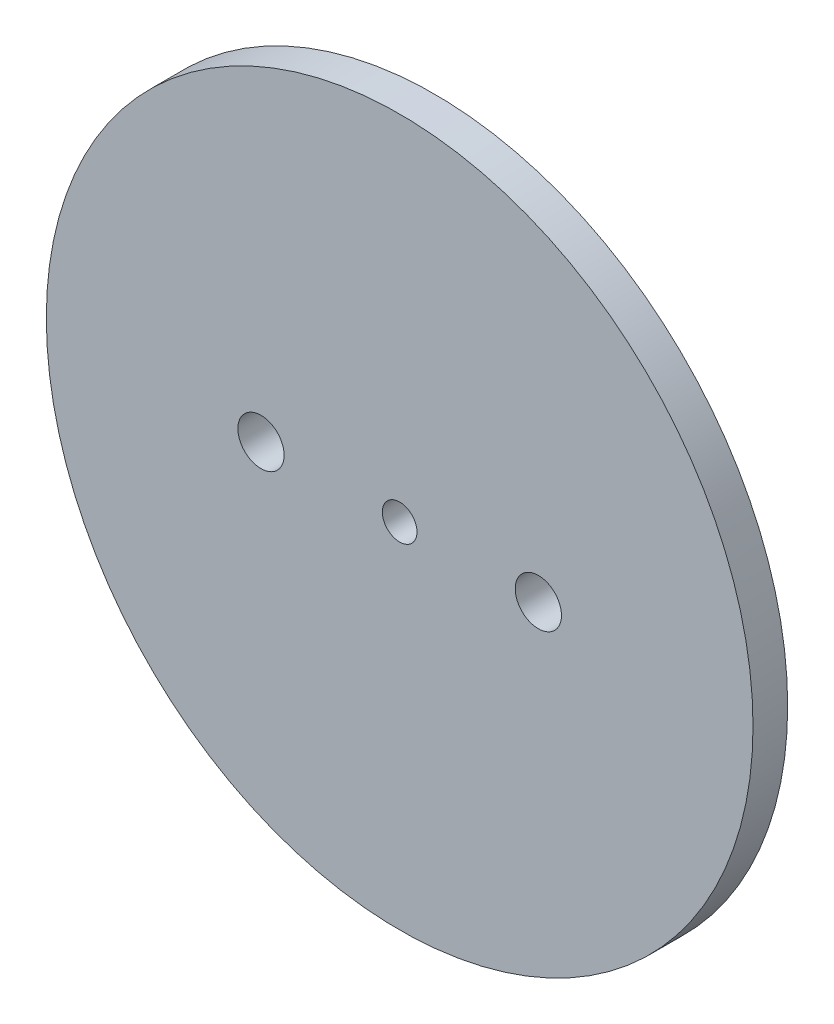
SolidWorks part; units mm, degrees
material "E-Glass Fiber"
ref_plane "Front Plane" through (0, 0, 0) normal (0, 0, 1) x (1, 0, 0)
ref_plane "Top Plane" through (0, 0, 0) normal (0, 1, 0) x (1, 0, 0)
ref_plane "Right Plane" through (0, 0, 0) normal (1, 0, 0) x (0, 0, -1)
sketch "Sketch1" plane through (0, 0, 0) normal (0, 0, 1) x (1, 0, 0)
  circle A0 centre (0, 0) radius 48.5394
  dimension "D1" = 97.0788
extrude "Boss-Extrude1" add sketch "Sketch1" along normal blind 4.7625
sketch "Sketch2" plane through (0, 0, 4.7625) normal (0, 0, 1) x (1, 0, 0)
  line L0 (-19.05, 0) -> (0, 0) construction
  line L1 (0, 0) -> (19.05, 0) construction
  circle A0 centre (0, 0) radius 2.3812
  circle A1 centre (19.05, 0) radius 3.175
  circle A2 centre (-19.05, 0) radius 3.175
  dimension "D1" = 4.7625
  dimension "D3" = 6.35
  dimension "D2" = 19.05
extrude "Cut-Extrude1" cut sketch "Sketch2" against normal through all
